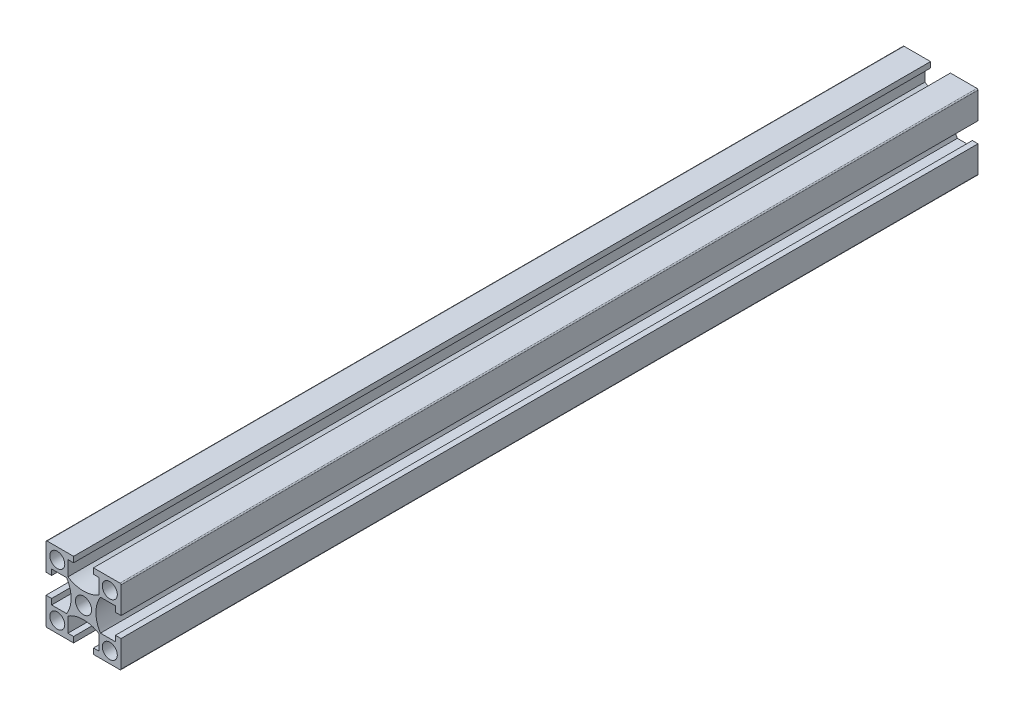
SolidWorks part; units mm, degrees
material "3.0255 (EN-AW 1350A)"
ref_plane "정면" through (0, 0, 0) normal (0, 0, 1) x (1, 0, 0)
ref_plane "윗면" through (0, 0, 0) normal (0, 1, 0) x (1, 0, 0)
ref_plane "우측면" through (0, 0, 0) normal (1, 0, 0) x (0, 0, -1)
sketch "스케치1" plane through (0, 0, 0) normal (0, 0, 1) x (1, 0, 0)
  line L0 (0, 32.0265) -> (0, -31.6588) construction
  line L1 (-10, 10) -> (-10, -10)
  line L2 (-10, 10) -> (10, 10)
  line L3 (-10, 2.65) -> (-8.5, 2.65)
  line L4 (13.6618, 0) -> (-11.6993, 0) construction
  line L5 (-8.5, 2.65) -> (-8.5, 4.15)
  line L6 (-8.5, 4.15) -> (-4.5032, 4.15)
  line L7 (-10, -2.65) -> (-8.5, -2.65)
  line L8 (-8.5, -2.65) -> (-8.5, -4.15)
  line L9 (-8.5, -4.15) -> (-4.5032, -4.15)
  line L10 (-10, -10) -> (10, -10)
  line L11 (10, 10) -> (10, -10)
  circle A0 centre (-7, 7) radius 2
  circle A1 centre (-7, -7) radius 2
  arc A2 (-4.5032, 4.15) -> (-4.5032, -4.15) centre (-11.0587, 0) cw
  circle A3 centre (0, 0) radius 2.15
  circle A4 centre (7, 7) radius 2
  circle A5 centre (7, -7) radius 2
  point P21 (-10, 0)
  point P23 (-3.3, 0)
  point P31 (0, -10)
  point P32 (0, 10)
  dimension "D3" = 4
  dimension "D9" = 6.7
  dimension "D10" = 4.3
  dimension "D11" = 7.7587
  dimension "D1" = 20
  dimension "D2" = 20
  dimension "D4" = 14
  dimension "D5" = 14
  dimension "D6" = 5.3
  dimension "D7" = 8.3
  dimension "D8" = 1.5
extrude "보스-돌출1" add sketch "스케치1" along normal blind 345 contours A0 | A4 | A3 | A5 | A1 | A2 L6 L5 L3 L1 L7 L8 L9 | L2 L11 L10 L1 region at (-6.6069, 0, 0) region at (-7, 7, 0) region at (-7, -7, 0) region at (0, 0, 0) region at (7, 7, 0) region at (7, -7, 0)
extrude "컷-돌출1" cut sketch "스케치1<3>" along normal up to next contours A2 L6 L5 L3 L1 L7 L8 L9 region at (-6.6069, 0, 0)
sketch "스케치1<3>" plane through (0, 0, 0) normal (0, 0, 1) x (1, 0, 0) same geometry as "스케치1"
pattern_circular "원형 패턴1" count 4 over 360 about axis through (0, 0, 345) along (0, 0, -1) of "컷-돌출1" reverse direction yes
fillet "필렛1" radius 0.3 4 edges at (10, -10, 172.5) (-10, -10, 172.5) (-10, 10, 172.5) (10, 10, 172.5)
sketch "스케치2" plane through (0, 0, 0) normal (1, 0, 0) x (0, 0, -1)
  circle A0 centre (-25, 0) radius 2.5
  dimension "D1" = 5
  dimension "D2" = 25
extrude "컷-돌출2" cut sketch "스케치2" against normal through all both and the other way through all
sketch "스케치4" plane through (0, 10, 0) normal (0, 1, 0) x (1, 0, 0)
  line L0 (0, -11) -> (0, 11) construction
  line L1 (2.65, -345) -> (9.7, -345) construction
  line L3 (-2.65, -106.62) -> (2.65, -106.62) construction
  line L4 (-2.65, -345) -> (-2.65, 0) construction
  line L5 (2.65, -345) -> (2.65, 0) construction
  line L6 (2.65, 0) -> (9.7, 0) construction
  circle A1 centre (0, -334) radius 2.5
  circle A2 centre (0, -127.62) radius 2.5
  circle A3 centre (0, -85.62) radius 2.5
  circle A4 centre (0, -303) radius 2.15
  dimension "D1" = 21
  dimension "D2" = 11
  dimension "D3" = 106.62
  dimension "D5" = 42
  dimension "D4" = 21
extrude "컷-돌출3" cut sketch "스케치4" against normal through all
sketch "스케치6" plane through (0, 10, 0) normal (0, 1, 0) x (1, 0, 0)
  line L0 (0, -11) -> (0, 11) construction
  line L1 (4.15, 0) -> (-4.15, 0) construction
  line L3 (-9.7, 0) -> (-2.65, 0) construction
  circle A0 centre (0, -236.9) radius 2.15
  circle A1 centre (0, -184.9) radius 2.15
  circle A2 centre (0, -10.15) radius 1.9797
  circle A3 centre (0, -62.15) radius 2.15
  dimension "D1" = 184.9
  dimension "D2" = 236.9
  dimension "D4" = 52
  dimension "D3" = 10.15
extrude "컷-돌출4" cut sketch "스케치6" against normal through all
sketch "스케치7" plane through (0, 10, 0) normal (0, 1, 0) x (1, 0, 0)
  line L0 (-10, -116.62) -> (10, -116.62)
  line L1 (-10, -345) -> (-10, 0) construction
  line L2 (10, 0) -> (10, -345) construction
  line L6 (-10, -116.62) -> (-10, 0)
  line L7 (-10, 0) -> (10, 0)
  line L8 (10, 0) -> (10, -116.62)
  circle A2 centre (0, -127.62) radius 2.5 construction
  dimension "D1" = 11
extrude "컷-돌출5" cut sketch "스케치7" against normal through all
